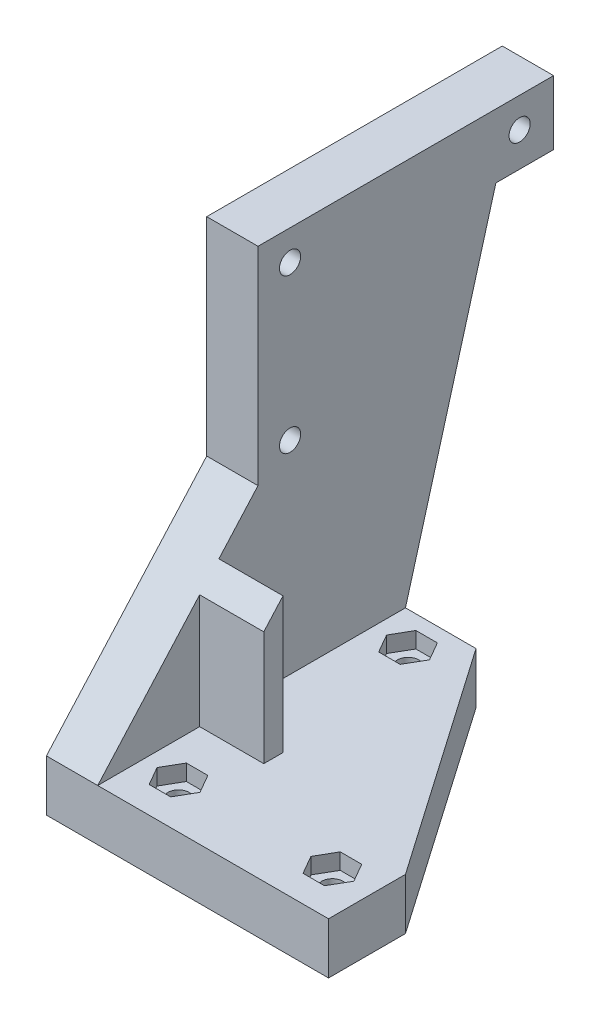
SolidWorks part; units mm, degrees
material "Copper"
ref_plane "Front Plane" through (0, 0, 0) normal (0, 0, 1) x (1, 0, 0)
ref_plane "Top Plane" through (0, 0, 0) normal (0, 1, 0) x (1, 0, 0)
ref_plane "Right Plane" through (0, 0, 0) normal (1, 0, 0) x (0, 0, -1)
sketch "Sketch1" plane through (0, 0, 0) normal (0, 1, 0) x (1, 0, 0)
  line L0 (-30.2016, 21.4588) -> (-19.2016, 21.4588)
  line L1 (5.7984, -26.5412) -> (5.7984, -14.5412)
  line L2 (-30.2016, 21.4588) -> (-30.2016, -26.5412)
  line L3 (-30.2016, -26.5412) -> (5.7984, -26.5412)
  line L4 (5.7984, -14.5412) -> (-19.2016, 21.4588)
  circle A0 centre (-24.6516, 16.3088) radius 1.65
  circle A1 centre (-24.6516, -19.4912) radius 1.65
  circle A2 centre (-0.6516, -19.4912) radius 1.65
  dimension "D3" = 3.3
  dimension "D6" = 3.3
  dimension "D9" = 3.3
  dimension "D1" = 48
  dimension "D2" = 5.15
  dimension "D4" = 5.55
  dimension "D5" = 11
  dimension "D7" = 35.8
  dimension "D8" = 5.55
  dimension "D10" = 24
  dimension "D11" = 35.8
  dimension "D12" = 12
extrude "Boss-Extrude1" add sketch "Sketch1" along normal blind 8
sketch "Sketch3" plane through (-30.2016, 0, 0) normal (-1, 0, 0) x (0, 0, 1)
  line L0 (-21.4588, 8) -> (26.5412, 8) construction
  line L1 (-44.5588, 58.3345) -> (-35.5588, 58.3345)
  line L2 (-35.5588, 58.3345) -> (-21.4588, 8)
  line L5 (26.5412, 8) -> (26.5412, 0) construction
  line L7 (-21.4588, 0) -> (26.5412, 0)
  line L8 (26.5412, 0) -> (26.5412, 8)
  line L9 (26.5412, 8) -> (1.5412, 36)
  line L10 (1.5412, 36) -> (1.5412, 68.3345)
  line L11 (1.5412, 68.3345) -> (-44.5588, 68.3345)
  line L12 (-44.5588, 68.3345) -> (-44.5588, 58.3345)
  line L14 (-21.4588, 8) -> (-21.4588, 0)
  circle A0 centre (-3.4588, 39.65) radius 1.65
  circle A1 centre (-3.4588, 63.65) radius 1.65
  circle A2 centre (-39.2588, 63.6645) radius 1.65
  dimension "D1" = 3.3
  dimension "D4" = 3.3
  dimension "D6" = 3.3
  dimension "D2" = 31.65
  dimension "D3" = 30
  dimension "D5" = 24
  dimension "D7" = 35.8
  dimension "D8" = 9
  dimension "D9" = 28
  dimension "D10" = 5
  dimension "D11" = 5.3
  dimension "D12" = 10
  dimension "D13" = 0
  dimension "D14" = 4.67
ref_axis "Axis1" through (-24.6516, 8, 19.4912) along (0, -1, 0)
extrude "Boss-Extrude2" add sketch "Sketch3" along normal blind 8
sketch "Sketch4" plane through (0, 8, 0) normal (0, 1, 0) x (1, 0, 0)
  line L1 (-26.3266, 13.4076) -> (-22.9766, 13.4076)
  line L2 (-22.9766, 13.4076) -> (-21.3016, 16.3088)
  line L3 (-21.3016, 16.3088) -> (-22.9766, 19.2099)
  line L4 (-22.9766, 19.2099) -> (-26.3266, 19.2099)
  line L5 (-26.3266, 19.2099) -> (-28.0016, 16.3088)
  line L6 (-28.0016, 16.3088) -> (-26.3266, 13.4076)
  line L7 (-22.9766, -16.5901) -> (-26.3266, -16.5901)
  line L8 (-26.3266, -16.5901) -> (-28.0016, -19.4912)
  line L9 (-28.0016, -19.4912) -> (-26.3266, -22.3924)
  line L10 (-26.3266, -22.3924) -> (-22.9766, -22.3924)
  line L11 (-22.9766, -22.3924) -> (-21.3016, -19.4912)
  line L12 (-21.3016, -19.4912) -> (-22.9766, -16.5901)
  line L13 (1.0234, -16.5901) -> (-2.3266, -16.5901)
  line L14 (-2.3266, -16.5901) -> (-4.0016, -19.4912)
  line L15 (-4.0016, -19.4912) -> (-2.3266, -22.3924)
  line L16 (-2.3266, -22.3924) -> (1.0234, -22.3924)
  line L17 (1.0234, -22.3924) -> (2.6984, -19.4912)
  line L18 (2.6984, -19.4912) -> (1.0234, -16.5901)
  circle A0 centre (-24.6516, 16.3088) radius 2.9012 construction
  circle A1 centre (-24.6516, -19.4912) radius 2.9012 construction
  circle A2 centre (-0.6516, -19.4912) radius 2.9012 construction
  dimension "D1" = 3.35
  dimension "D2" = 3.35
  dimension "D3" = 3.35
extrude "Cut-Extrude1" cut sketch "Sketch4" against normal blind 2.5
sketch "Sketch5" plane through (-30.2016, 0, 0) normal (1, 0, 0) x (0, 0, -1)
  line L0 (21.4588, 8) -> (-26.5412, 8) construction
  line L1 (-10.6412, 8) -> (-7.6412, 8)
  line L2 (-10.6412, 8) -> (-10.6412, 25.808)
  line L3 (-10.6412, 25.808) -> (-7.6412, 29.168)
  line L4 (-7.6412, 8) -> (-7.6412, 29.168)
  line L5 (-26.5412, 8) -> (-1.5412, 36) construction
  circle A0 centre (3.4588, 39.65) radius 1.65 construction
  dimension "D1" = 11.1
  dimension "D2" = 3
extrude "Boss-Extrude3" add sketch "Sketch5" along direction (1, 0, 0) on the side of the normal blind 10
